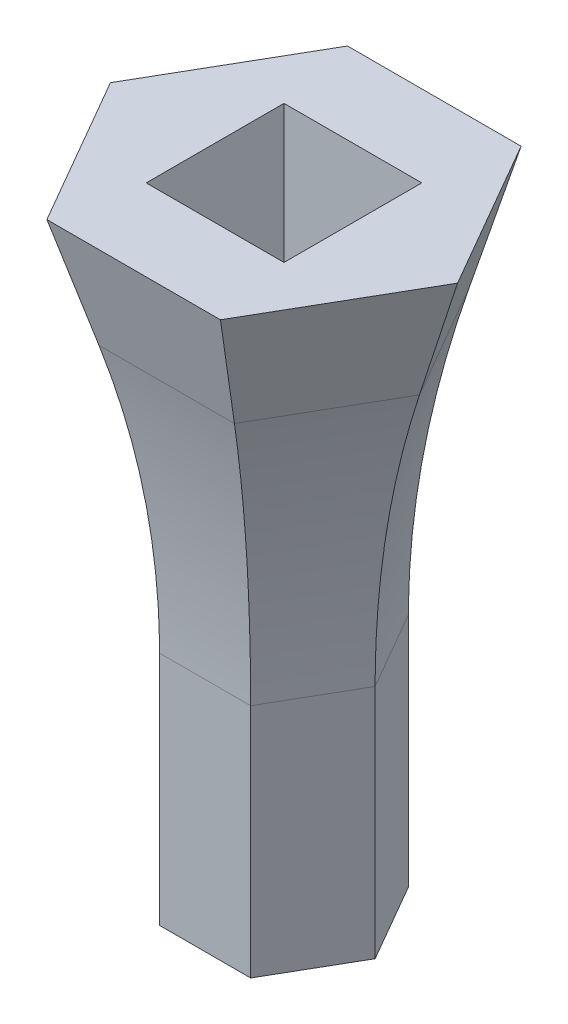
SolidWorks part; units mm, degrees
ref_plane "Plan de face" through (0, 0, 0) normal (0, 0, 1) x (1, 0, 0)
ref_plane "Plan de dessus" through (0, 0, 0) normal (0, 1, 0) x (1, 0, 0)
ref_plane "Plan de droite" through (0, 0, 0) normal (1, 0, 0) x (0, 0, -1)
sketch "Esquisse1" plane through (0, 0, 0) normal (0, 1, 0) x (1, 0, 0)
  line L1 (1.8187, -3.15) -> (3.6373, 0)
  line L2 (3.6373, 0) -> (1.8187, 3.15)
  line L3 (1.8187, 3.15) -> (-1.8187, 3.15)
  line L4 (-1.8187, 3.15) -> (-3.6373, 0)
  line L5 (-3.6373, 0) -> (-1.8187, -3.15)
  line L6 (-1.8187, -3.15) -> (1.8187, -3.15)
  circle A0 centre (0, 0) radius 3.15 construction
  dimension "D1" = 6.3
extrude "Boss.-Extru.1" add sketch "Esquisse1" along normal blind 15
sketch3d "Esquisse3D1" plane through (0, 0, 0) normal (0, 0, 1) x (1, 0, 0)
  dimension "D1" = 25
sketch "Esquisse3" plane through (0, 25, 0) normal (0, 1, 0) x (1, 0, 0)
  line L1 (3.4641, -6) -> (6.9282, 0)
  line L2 (6.9282, 0) -> (3.4641, 6)
  line L3 (3.4641, 6) -> (-3.4641, 6)
  line L4 (-3.4641, 6) -> (-6.9282, 0)
  line L5 (-6.9282, 0) -> (-3.4641, -6)
  line L6 (-3.4641, -6) -> (3.4641, -6)
  circle A0 centre (0, 0) radius 6 construction
  point P1 (0, 6)
  point P10 (0, 0)
  dimension "D1" = 12
loft "Lissage1" add profiles "Esquisse3" section face at (0, 15, 0) section "Esquisse3"
sketch "Esquisse4" plane through (0, 25, 0) normal (0, 1, 0) x (1, 0, 0)
  line L1 (-2.75, 2.75) -> (2.75, 2.75)
  line L2 (-2.75, 2.75) -> (-2.75, -2.75)
  line L3 (-2.75, -2.75) -> (2.75, -2.75)
  line L4 (2.75, 2.75) -> (2.75, -2.75)
  line L5 (-2.75, 2.75) -> (2.75, -2.75) construction
  line L6 (-2.75, -2.75) -> (2.75, 2.75) construction
  point P0 (0, 0)
  dimension "D1" = 5.5
  dimension "D2" = 5.5
extrude "Enlèv. mat.-Extru.1" cut sketch "Esquisse4" against normal blind 6
fillet "Congé2" radius 40 6 edges at (0, 15, 3.15) (2.728, 15, 1.575) (2.728, 15, -1.575) (0, 15, -3.15) (-2.728, 15, -1.575) (-2.728, 15, 1.575)
